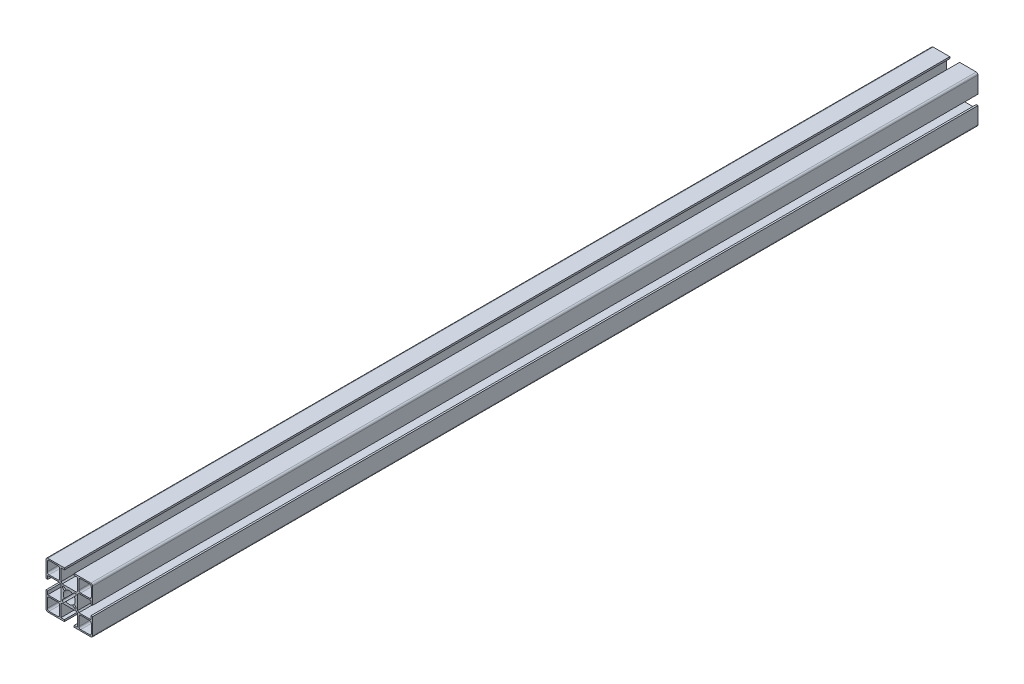
SolidWorks part; units mm, degrees
note: '?' marks a value the reader was unsure of.
material "6063-T5"
ref_plane "前视基准面" through (0, 0, 0) normal (0, 0, 1) x (1, 0, 0)
ref_plane "上视基准面" through (0, 0, 0) normal (0, 1, 0) x (1, 0, 0)
ref_plane "右视基准面" through (0, 0, 0) normal (1, 0, 0) x (0, 0, -1)
sketch "草图1" plane through (0, 0, 0) normal (0, 0, 1) x (1, 0, 0)
  line L0 (-6.0893, -7.15) -> (6.0893, -7.15)
  line L1 (7.15, -8.2107) -> (6.0893, -7.15)
  line L2 (-7.15, -8.2107) -> (-6.0893, -7.15)
  line L3 (7.15, -8.2107) -> (7.15, -18.5)
  line L4 (-7.15, -8.2107) -> (-7.15, -18.5)
  line L5 (4.2, -18.5) -> (7.15, -18.5)
  line L6 (-4.2, -18.5) -> (-7.15, -18.5)
  line L7 (4.2, -18.5) -> (4.2, -20)
  line L8 (-4.2, -18.5) -> (-4.2, -20)
  line L9 (4.2, -20) -> (18.5, -20)
  line L10 (-4.2, -20) -> (-18.5, -20)
  line L11 (20, -18.5) -> (20, -4.2)
  line L12 (-20, -18.5) -> (-20, -4.2)
  line L13 (20, -4.2) -> (18.5, -4.2)
  line L14 (-20, -4.2) -> (-18.5, -4.2)
  line L15 (18.5, -4.2) -> (18.5, -7.15)
  line L16 (-18.5, -4.2) -> (-18.5, -7.15)
  line L17 (18.5, -7.15) -> (8.2107, -7.15)
  line L18 (-18.5, -7.15) -> (-8.2107, -7.15)
  line L19 (8.2107, -7.15) -> (7.15, -6.0893)
  line L20 (-8.2107, -7.15) -> (-7.15, -6.0893)
  line L21 (7.15, 6.0893) -> (7.15, -6.0893)
  line L22 (-7.15, 6.0893) -> (-7.15, -6.0893)
  line L23 (8.2107, 7.15) -> (7.15, 6.0893)
  line L24 (-8.2107, 7.15) -> (-7.15, 6.0893)
  line L25 (18.5, 7.15) -> (8.2107, 7.15)
  line L26 (-18.5, 7.15) -> (-8.2107, 7.15)
  line L27 (18.5, 4.2) -> (18.5, 7.15)
  line L28 (-18.5, 4.2) -> (-18.5, 7.15)
  line L29 (20, 4.2) -> (18.5, 4.2)
  line L30 (-20, 4.2) -> (-18.5, 4.2)
  line L31 (20, 18.5) -> (20, 4.2)
  line L32 (-20, 18.5) -> (-20, 4.2)
  line L33 (4.2, 20) -> (18.5, 20)
  line L34 (-4.2, 20) -> (-18.5, 20)
  line L35 (4.2, 18.5) -> (4.2, 20)
  line L36 (-4.2, 18.5) -> (-4.2, 20)
  line L37 (4.2, 18.5) -> (7.15, 18.5)
  line L38 (-4.2, 18.5) -> (-7.15, 18.5)
  line L39 (7.15, 8.2107) -> (7.15, 18.5)
  line L40 (-7.15, 8.2107) -> (-7.15, 18.5)
  line L41 (7.15, 8.2107) -> (6.0893, 7.15)
  line L42 (-7.15, 8.2107) -> (-6.0893, 7.15)
  line L43 (6.0893, 7.15) -> (-6.0893, 7.15)
  line L44 (17.4, 8.25) -> (9.75, 8.25)
  line L45 (8.25, 9.75) -> (8.25, 17.4)
  line L46 (18.9, 17.4) -> (18.9, 9.75)
  line L47 (9.75, 18.9) -> (17.4, 18.9)
  line L48 (-8.25, 17.4) -> (-8.25, 9.75)
  line L49 (-17.4, 18.9) -> (-9.75, 18.9)
  line L50 (-9.75, 8.25) -> (-17.4, 8.25)
  line L51 (-18.9, 9.75) -> (-18.9, 17.4)
  line L52 (-17.4, -8.25) -> (-9.75, -8.25)
  line L53 (-8.25, -9.75) -> (-8.25, -17.4)
  line L54 (-18.9, -17.4) -> (-18.9, -9.75)
  line L55 (-9.75, -18.9) -> (-17.4, -18.9)
  line L56 (8.25, -17.4) -> (8.25, -9.75)
  line L57 (17.4, -18.9) -> (9.75, -18.9)
  line L58 (9.75, -8.25) -> (17.4, -8.25)
  line L59 (18.9, -9.75) -> (18.9, -17.4)
  line L60 (-4.2433, 2.8291) -> (-5.6569, 4.2426)
  line L61 (-5.6569, -4.2426) -> (-4.2433, -2.8291)
  line L62 (-4.2426, 5.6569) -> (-2.8291, 4.2433)
  line L63 (-2.8291, -4.2433) -> (-4.2426, -5.6569)
  line L64 (2.8291, 4.2433) -> (4.2426, 5.6569)
  line L65 (4.2426, -5.6569) -> (2.8291, -4.2433)
  line L66 (5.6569, 4.2426) -> (4.2433, 2.8291)
  line L67 (4.2433, -2.8291) -> (5.6569, -4.2426)
  arc A0 (18.5, -20) -> (20, -18.5) centre (18.5, -18.5) ccw
  arc A1 (-20, -18.5) -> (-18.5, -20) centre (-18.5, -18.5) ccw
  arc A2 (20, 18.5) -> (18.5, 20) centre (18.5, 18.5) ccw
  arc A3 (-18.5, 20) -> (-20, 18.5) centre (-18.5, 18.5) ccw
  arc A4 (8.25, 9.75) -> (9.75, 8.25) centre (9.75, 9.75) ccw
  arc A5 (17.4, 8.25) -> (18.9, 9.75) centre (17.4, 9.75) ccw
  arc A6 (9.75, 18.9) -> (8.25, 17.4) centre (9.75, 17.4) ccw
  arc A7 (18.9, 17.4) -> (17.4, 18.9) centre (17.4, 17.4) ccw
  arc A8 (-8.25, 17.4) -> (-9.75, 18.9) centre (-9.75, 17.4) ccw
  arc A9 (-9.75, 8.25) -> (-8.25, 9.75) centre (-9.75, 9.75) ccw
  arc A10 (-17.4, 18.9) -> (-18.9, 17.4) centre (-17.4, 17.4) ccw
  arc A11 (-18.9, 9.75) -> (-17.4, 8.25) centre (-17.4, 9.75) ccw
  arc A12 (-8.25, -9.75) -> (-9.75, -8.25) centre (-9.75, -9.75) ccw
  arc A13 (-17.4, -8.25) -> (-18.9, -9.75) centre (-17.4, -9.75) ccw
  arc A14 (-9.75, -18.9) -> (-8.25, -17.4) centre (-9.75, -17.4) ccw
  arc A15 (-18.9, -17.4) -> (-17.4, -18.9) centre (-17.4, -17.4) ccw
  arc A16 (8.25, -17.4) -> (9.75, -18.9) centre (9.75, -17.4) ccw
  arc A17 (9.75, -8.25) -> (8.25, -9.75) centre (9.75, -9.75) ccw
  arc A18 (17.4, -18.9) -> (18.9, -17.4) centre (17.4, -17.4) ccw
  arc A19 (18.9, -9.75) -> (17.4, -8.25) centre (17.4, -9.75) ccw
  arc A20 (-4.2433, 2.8291) -> (-4.2433, -2.8291) centre (0, 0) ccw
  arc A21 (-4.2426, 5.6569) -> (-5.6569, 4.2426) centre (-4.9497, 4.9497) ccw
  arc A22 (-5.6569, -4.2426) -> (-4.2426, -5.6569) centre (-4.9497, -4.9497) ccw
  arc A23 (2.8291, 4.2433) -> (-2.8291, 4.2433) centre (0, 0) ccw
  arc A24 (-2.8291, -4.2433) -> (2.8291, -4.2433) centre (0, 0) ccw
  arc A25 (5.6569, 4.2426) -> (4.2426, 5.6569) centre (4.9497, 4.9497) ccw
  arc A26 (4.2426, -5.6569) -> (5.6569, -4.2426) centre (4.9497, -4.9497) ccw
  arc A27 (4.2433, -2.8291) -> (4.2433, 2.8291) centre (0, 0) ccw
extrude "凸台-拉伸1" add sketch "草图1" along normal blind 760
ref_axis "基准轴" through (0, 0, 0) along (0, 0, 1)?
ref_plane "基准面" through (0, 0, -20) normal (0, 0, -1) x (-1, 0, 0)
hole_wizard "螺纹孔E" [suppressed] positions "草图3" profile "草图2" tap size "M12" standard "GB"
sketch "草图3" plane through (0, 0, 300) normal (0, 0, 1) x (1, 0, 0)
  point P0 (0, 0)
sketch "草图2" plane through (0, 0, 300) normal (1, 0, 0) x (0, -1, 0)
  line L0 (0, 0) -> (0, 31.8174)
  line L1 (0, 31.8174) -> (5.105, 28.75)
  line L2 (5.105, 28.75) -> (5.105, 0)
  line L5 (5.105, 0) -> (0, 0)
  line L10 (0, 31.8174) -> (-5.105, 28.75) construction
  line L11 (0, -6.35) -> (0, 107.95) construction
  dimension "螺纹孔钻头直径" = 10.21
  dimension "螺纹孔钻头深度" = 28.75
  dimension "导头角度" = 118
cosmetic thread "孔螺蚊线1" [suppressed] parameters "D1"=20, "D2"=12
hole_wizard "螺纹孔S" [suppressed] positions "草图5" profile "草图4" tap size "M12" standard "GB"
sketch "草图5" plane through (0, 0, 0) normal (0, 0, -1) x (-1, 0, 0)
  point P0 (0, 0)
sketch "草图4" plane through (0, 0, 0) normal (1, 0, 0) x (0, 1, 0)
  line L0 (0, 0) -> (0, 31.8174)
  line L1 (0, 31.8174) -> (5.105, 28.75)
  line L2 (5.105, 28.75) -> (5.105, 0)
  line L5 (5.105, 0) -> (0, 0)
  line L10 (0, 31.8174) -> (-5.105, 28.75) construction
  line L11 (0, -6.35) -> (0, 107.95) construction
  dimension "螺纹孔钻头直径" = 10.21
  dimension "螺纹孔钻头深度" = 28.75
  dimension "导头角度" = 118
cosmetic thread "孔螺蚊线2" [suppressed] parameters "D1"=20, "D2"=12
other "内孔SA1" [suppressed] parameters "D1"=16.8
sketch "草图6" plane through (0, 20, 0) normal (0, 1, 0) x (1, 0, 0)
  line L0 (-4.2, 0) -> (-18.5, 0) construction
  line L1 (0, -22) -> (0, 22) construction
  circle A0 centre (0, -19) radius 10
  dimension "D1" = 20
  dimension "D2" = 19
other "内孔EA1" [suppressed] parameters "D1"=16.8
sketch "草图7" plane through (0, 20, 0) normal (0, 1, 0) x (1, 0, 0)
  line L0 (-4.2, -300) -> (-18.5, -300) construction
  line L1 (0, -22) -> (0, 22) construction
  circle A0 centre (0, -281) radius 10
  dimension "D1" = 20
  dimension "D2" = 19
other "内孔SB1" [suppressed] parameters "D1"=16.8
sketch "草图8" plane through (-20, 0, 0) normal (-1, 0, 0) x (0, 0, 1)
  line L0 (0, -4.2) -> (0, -18.5) construction
  line L1 (22, 0) -> (-22, 0) construction
  circle A0 centre (19, 0) radius 10
  dimension "D1" = 20
  dimension "D2" = 19
other "内孔EB1" [suppressed] parameters "D1"=16.8
sketch "草图9" plane through (-20, 0, 0) normal (-1, 0, 0) x (0, 0, 1)
  line L0 (300, -4.2) -> (300, -18.5) construction
  line L1 (22, 0) -> (-22, 0) construction
  circle A0 centre (281, 0) radius 10
  dimension "D1" = 20
  dimension "D2" = 19
other "内孔SC1" [suppressed] parameters "D1"=16.8
sketch "草图10" plane through (0, -20, 0) normal (0, -1, 0) x (-1, 0, 0)
  line L0 (-4.2, 0) -> (-18.5, 0) construction
  line L1 (0, 22) -> (0, -22) construction
  circle A0 centre (0, -19) radius 10
  dimension "D1" = 20
  dimension "D2" = 19
other "内孔EC1" [suppressed] parameters "D1"=16.8
sketch "草图11" plane through (0, -20, 0) normal (0, -1, 0) x (-1, 0, 0)
  line L0 (-4.2, -300) -> (-18.5, -300) construction
  line L1 (0, 22) -> (0, -22) construction
  circle A0 centre (0, -281) radius 10
  dimension "D1" = 20
  dimension "D2" = 19
other "内孔SD1" [suppressed] parameters "D1"=16.8
sketch "草图12" plane through (20, 0, 0) normal (1, 0, 0) x (0, 0, -1)
  line L0 (0, 4.2) -> (0, 18.5) construction
  line L1 (22, 0) -> (-22, 0) construction
  circle A0 centre (-19, 0) radius 10
  dimension "D1" = 20
  dimension "D2" = 19
other "内孔ED1" [suppressed] parameters "D1"=16.8
sketch "草图13" plane through (20, 0, 0) normal (1, 0, 0) x (0, 0, -1)
  line L0 (-300, 4.2) -> (-300, 18.5) construction
  line L1 (22, 0) -> (-22, 0) construction
  circle A0 centre (-281, 0) radius 10
  dimension "D1" = 20
  dimension "D2" = 19
other "锚孔SA1" [suppressed] parameters "D1"=40
sketch "草图14" plane through (0, 20, 0) normal (0, 1, 0) x (1, 0, 0)
  line L0 (-4.2, 0) -> (-18.5, 0) construction
  line L1 (0, -22) -> (0, 22) construction
  circle A0 centre (0, -30.2) radius 8.5
  dimension "D1" = 17
  dimension "D2" = 30.2
other "锚孔EA1" [suppressed] parameters "D1"=40
sketch "草图15" plane through (0, 20, 0) normal (0, 1, 0) x (1, 0, 0)
  line L0 (-4.2, -300) -> (-18.5, -300) construction
  line L1 (0, -22) -> (0, 22) construction
  circle A0 centre (0, -269.8) radius 8.5
  dimension "D1" = 17
  dimension "D2" = 30.2
other "锚孔SB1" [suppressed] parameters "D1"=40
sketch "草图16" plane through (-20, 0, 0) normal (-1, 0, 0) x (0, 0, 1)
  line L0 (0, -4.2) -> (0, -18.5) construction
  line L1 (22, 0) -> (-22, 0) construction
  circle A0 centre (30.2, 0) radius 8.5
  dimension "D1" = 17
  dimension "D2" = 30.2
other "锚孔EB1" [suppressed] parameters "D1"=40
sketch "草图17" plane through (-20, 0, 0) normal (-1, 0, 0) x (0, 0, 1)
  line L0 (300, -4.2) -> (300, -18.5) construction
  line L1 (22, 0) -> (-22, 0) construction
  circle A0 centre (269.8, 0) radius 8.5
  dimension "D1" = 17
  dimension "D2" = 30.2
other "锚孔SC1" [suppressed] parameters "D1"=40.1
sketch "草图18" plane through (0, -20, 0) normal (0, -1, 0) x (-1, 0, 0)
  line L0 (-4.2, 0) -> (-18.5, 0) construction
  line L1 (0, 22) -> (0, -22) construction
  circle A0 centre (0, -30.2) radius 8.5
  dimension "D1" = 17
  dimension "D2" = 30.2
other "锚孔EC1" [suppressed] parameters "D1"=40.1
sketch "草图19" plane through (0, -20, 0) normal (0, -1, 0) x (-1, 0, 0)
  line L0 (-4.2, -300) -> (-18.5, -300) construction
  line L1 (0, 22) -> (0, -22) construction
  circle A0 centre (0, -269.8) radius 8.5
  dimension "D1" = 17
  dimension "D2" = 30.2
other "锚孔SD1" [suppressed] parameters "D1"=40.1
sketch "草图20" plane through (20, 0, 0) normal (1, 0, 0) x (0, 0, -1)
  line L0 (0, 4.2) -> (0, 18.5) construction
  line L1 (22, 0) -> (-22, 0) construction
  circle A0 centre (-30.2, 0) radius 8.5
  dimension "D1" = 17
  dimension "D2" = 30.2
other "锚孔ED1" [suppressed] parameters "D1"=40.1
sketch "草图21" plane through (20, 0, 0) normal (1, 0, 0) x (0, 0, -1)
  line L0 (-300, 4.2) -> (-300, 18.5) construction
  line L1 (22, 0) -> (-22, 0) construction
  circle A0 centre (-269.8, 0) radius 8.5
  dimension "D1" = 17
  dimension "D2" = 30.2
